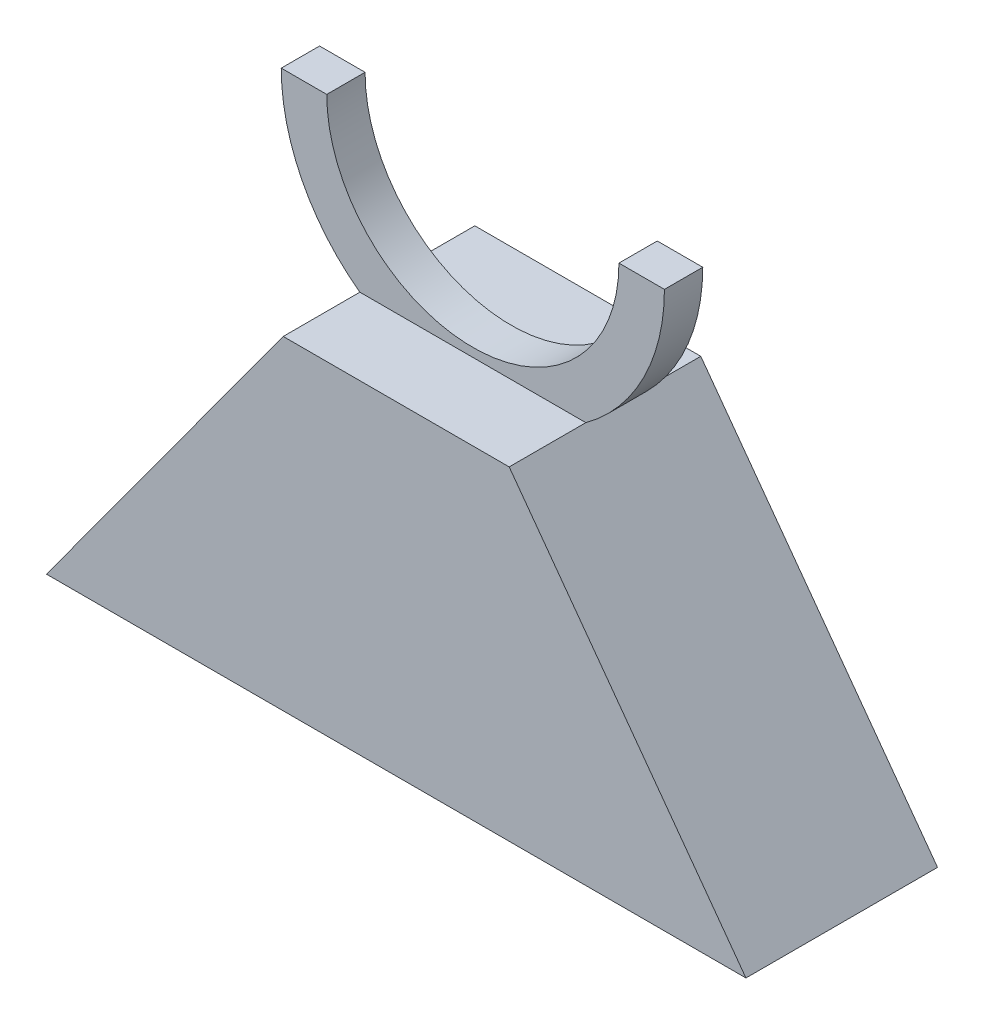
SolidWorks part; units mm, degrees
material "ABS"
ref_plane "Plan de face" through (0, 0, 0) normal (0, 0, 1) x (1, 0, 0)
ref_plane "Plan de dessus" through (0, 0, 0) normal (0, 1, 0) x (1, 0, 0)
ref_plane "Plan de droite" through (0, 0, 0) normal (1, 0, 0) x (0, 0, -1)
sketch "Esquisse1" plane through (0, 0, 0) normal (0, 0, 1) x (1, 0, 0)
  line L0 (-20, 0) -> (-15.25, 0)
  line L1 (15.25, 0) -> (20, 0)
  arc A0 (15.25, 0) -> (-15.25, 0) centre (0, 0) cw
  arc A1 (20, 0) -> (-20, 0) centre (0, 0) cw
extrude "Boss.-Extru.1" add sketch "Esquisse1" along normal blind 2 and the other way blind 2
sketch "Esquisse2" plane through (0, 0, 0) normal (0, 0, 1) x (1, 0, 0)
  line L0 (-36.5088, -50) -> (-11.7941, -16.1524)
  line L1 (36.5088, -50) -> (11.7941, -16.1524)
  line L2 (-36.5088, -50) -> (36.5088, -50)
  line L3 (11.7941, -16.1524) -> (-11.7941, -16.1524)
  arc A1 (-20, 0) -> (20, 0) centre (0, 0) ccw construction
extrude "Boss.-Extru.3" add sketch "Esquisse2" along normal blind 10 and the other way blind 10 contours L1 L0 L2 region at (0, -35.9626, 0)
